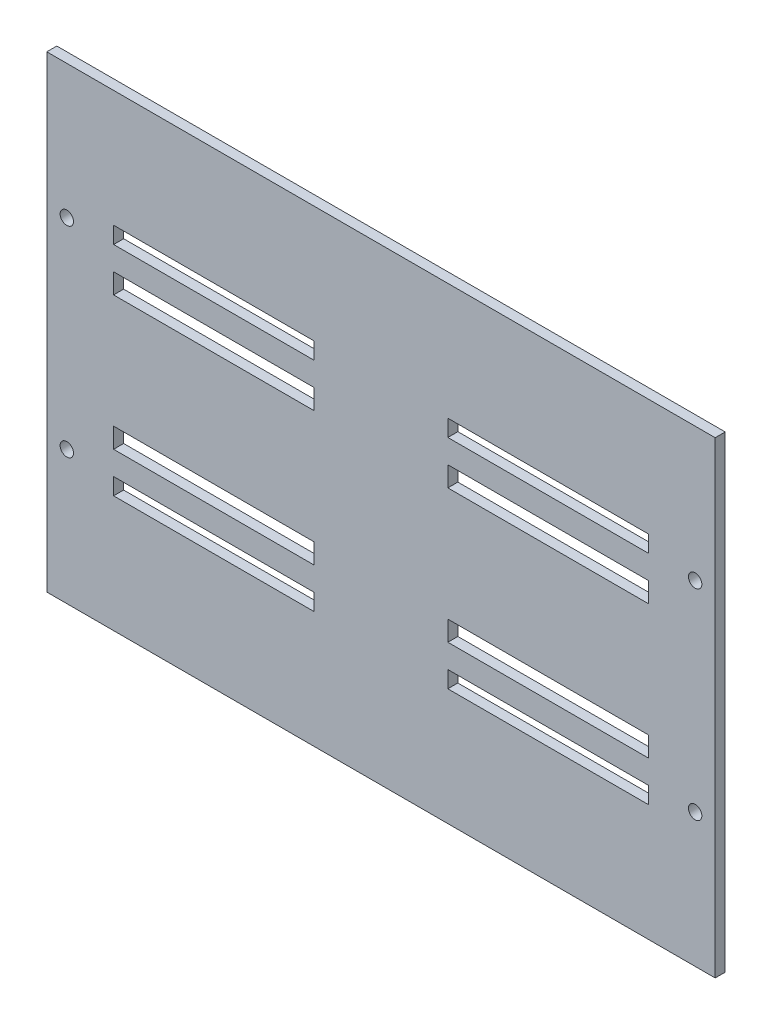
SolidWorks part; units mm, degrees
ref_plane "Front" through (0, 0, 0) normal (0, 0, 1) x (1, 0, 0)
ref_plane "Top" through (0, 0, 0) normal (0, 1, 0) x (1, 0, 0)
ref_plane "Right" through (0, 0, 0) normal (1, 0, 0) x (0, 0, -1)
sketch "草图2" plane through (0, 0, 0) normal (0, 0, 1) x (1, 0, 0)
  line L1 (-100, -70) -> (100, -70)
  line L2 (-100, -70) -> (-100, 70)
  line L3 (-100, 70) -> (100, 70)
  line L4 (100, -70) -> (100, 70)
  line L5 (-100, -70) -> (100, 70) construction
  line L6 (-100, 70) -> (100, -70) construction
  point P0 (0, 0)
  dimension "D1" = 140
  dimension "D2" = 200
extrude "凸台-拉伸1" add sketch "草图2" along normal blind 3
sketch "草图3" plane through (0, 0, 3) normal (0, 0, 1) x (1, 0, 0)
  line L0 (94, -30) -> (94, 30) construction
  line L2 (100, -70) -> (100, 70) construction
  circle A0 centre (94, 30) radius 2
  circle A1 centre (94, -30) radius 2
  point P4 (94, 0)
  dimension "D1" = 4
  dimension "D2" = 60
  dimension "D3" = 6
extrude "切除-拉伸1" cut sketch "草图3" against normal blind 3 contours A0 | A1
sketch "草图4" plane through (0, 0, 3) normal (0, 0, 1) x (1, 0, 0)
  line L0 (-100, 0) -> (100, 0) construction
  line L1 (-100, 70) -> (-100, -70) construction
  line L2 (100, -70) -> (100, 70) construction
  line L4 (20, 23) -> (80, 23)
  line L5 (20, 23) -> (20, 17)
  line L6 (20, 17) -> (80, 17)
  line L7 (80, 23) -> (80, 17)
  line L8 (20, 23) -> (80, 17) construction
  line L9 (20, 17) -> (80, 23) construction
  line L10 (20, -23) -> (80, -23)
  line L11 (20, -23) -> (20, -17)
  line L12 (20, -17) -> (80, -17)
  line L13 (80, -23) -> (80, -17)
  line L14 (20, -23) -> (80, -17) construction
  line L15 (20, -17) -> (80, -23) construction
  point P6 (50, 20)
  point P11 (50, -20)
  point P16 (0, 0)
  dimension "D1" = 34
  dimension "D2" = 6
  dimension "D3" = 6
  dimension "D4" = 17
  dimension "D5" = 60
  dimension "D6" = 20
extrude "切除-拉伸2" cut sketch "草图4" against normal blind 10
sketch "草图5" plane through (0, 0, 0) normal (0, 0, -1) x (-1, 0, 0)
  line L0 (-20, 17) -> (-20, 23) construction
  line L1 (-80, 30.0611) -> (-20, 30.0611)
  line L2 (-80, 30.0611) -> (-80, 35.0611)
  line L3 (-80, 35.0611) -> (-20, 35.0611)
  line L4 (-20, 30.0611) -> (-20, 35.0611)
  line L5 (-80, 30.0611) -> (-20, 35.0611) construction
  line L6 (-80, 35.0611) -> (-20, 30.0611) construction
  line L7 (-80, 23) -> (-80, 17) construction
  point P0 (-50, 32.5611)
  dimension "D1" = 5
extrude "切除-拉伸3" cut sketch "草图5" against normal blind 6
mirror "镜向1" about plane through (0, 0, 0) normal (0, 1, 0) of "切除-拉伸3"
ref_plane "基准面1" through (0, 0, 0) normal (-1, 0, 0) x (0, 0, 1)
mirror "镜向2" about plane through (0, 0, 0) normal (-1, 0, 0) of "切除-拉伸1", "镜向1", "切除-拉伸2", "切除-拉伸3"
